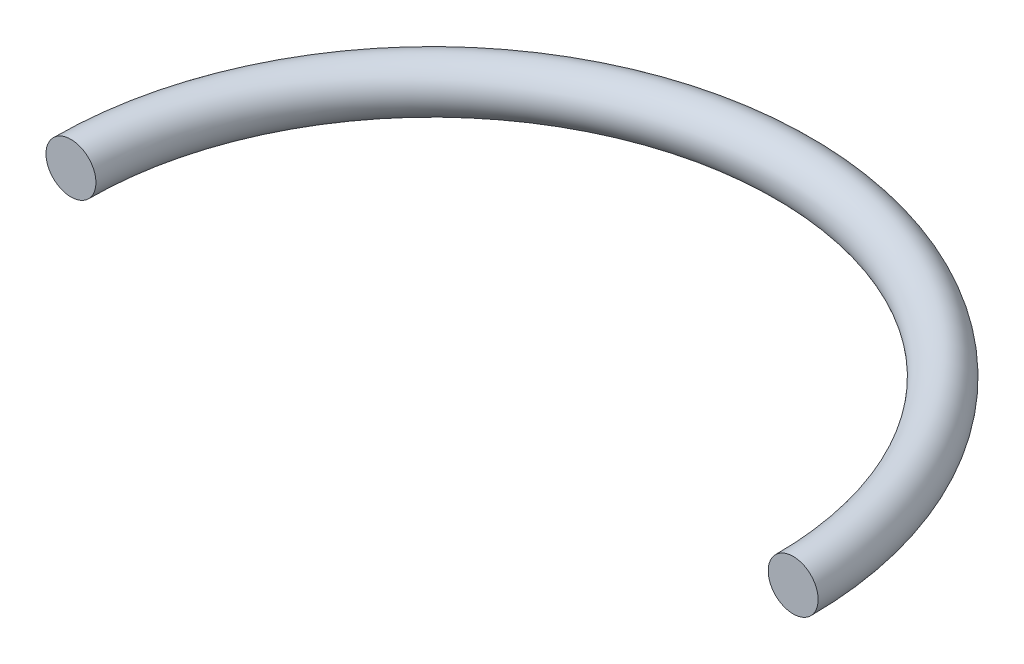
SolidWorks part; units mm, degrees
ref_plane "Front Plane" through (0, 0, 0) normal (0, 0, 1) x (1, 0, 0)
ref_plane "Top Plane" through (0, 0, 0) normal (0, 1, 0) x (1, 0, 0)
ref_plane "Right Plane" through (0, 0, 0) normal (1, 0, 0) x (0, 0, -1)
sketch "Sketch1" plane through (0, 0, 0) normal (0, 0, 1) x (1, 0, 0)
  line L0 (0, 7.4127) -> (0, -7.2743) construction
  circle A0 centre (-9.4, 0) radius 0.65
  point P2 (-9.4, 0)
  point P3 (9.4, 0)
  dimension "D1" = 1.3
  dimension "D2" = 9.4
revolve "Revolve1" add sketch "Sketch1" angle 180 about L0
ref_axis "Axis1" through (-9.4, 0, 0) along (0, 0, 1)
ref_axis "Axis2" through (9.4, 0, 0) along (0, 0, 1)
